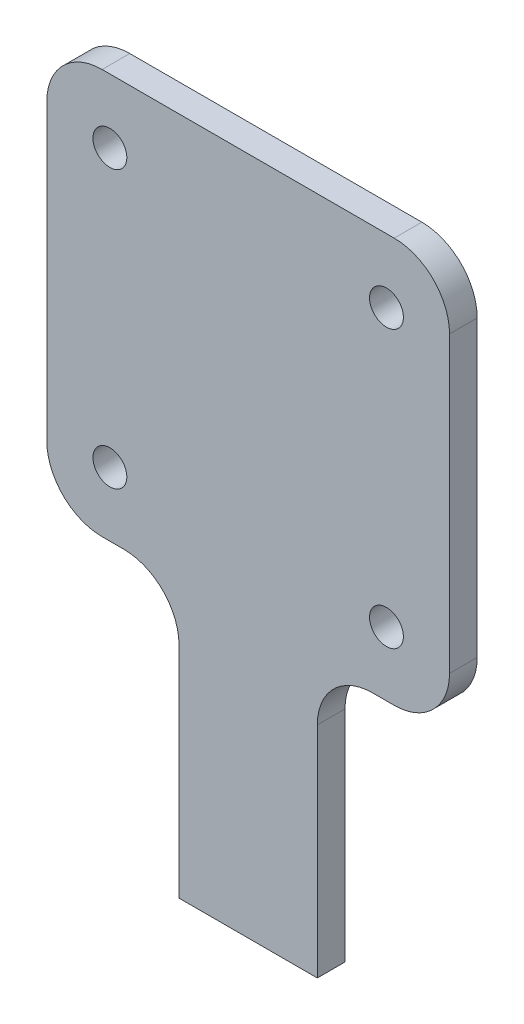
SolidWorks part; units mm, degrees
ref_plane "Front Plane" through (0, 0, 0) normal (0, 0, 1) x (1, 0, 0)
ref_plane "Top Plane" through (0, 0, 0) normal (0, 1, 0) x (1, 0, 0)
ref_plane "Right Plane" through (0, 0, 0) normal (1, 0, 0) x (0, 0, -1)
sketch "Sketch3" plane through (0, 0, 0) normal (0, 0, 1) x (1, 0, 0)
  line L0 (5, 19.8536) -> (14.56, 19.8536)
  line L2 (5, 19.8536) -> (5, 0)
  line L3 (5, 0) -> (-5, 0)
  line L4 (-5, 19.8536) -> (-5, 0)
  line L7 (-14.56, 49.1136) -> (14.56, 49.1136)
  line L8 (-14.56, 49.1136) -> (-14.56, 19.8536)
  line L9 (-14.56, 19.8536) -> (-5, 19.8536)
  line L10 (14.56, 49.1136) -> (14.56, 19.8536)
  line L13 (-14.56, 19.8536) -> (14.56, 19.8536) construction
  point P5 (0, 0)
  dimension "D1" = 10
extrude "Boss-Extrude1" add sketch "Sketch3" along normal mid plane 2
sketch "Sketch4" plane through (0, 0, -1) normal (0, 0, -1) x (-1, 0, 0)
  circle A0 centre (-10, 24.4836) radius 1.225 construction
  circle A1 centre (10, 24.4836) radius 1.225 construction
  circle A2 centre (10, 44.4836) radius 1.225 construction
  circle A3 centre (-10, 44.4836) radius 1.225 construction
  circle A4 centre (-10, 24.4836) radius 1.225
  circle A5 centre (10, 24.4836) radius 1.225
  circle A6 centre (10, 44.4836) radius 1.225
  circle A7 centre (-10, 44.4836) radius 1.225
  circle A8 centre (-10, 44.4836) radius 1.725
  circle A9 centre (10, 44.4836) radius 1.725
  circle A10 centre (-10, 24.4836) radius 1.725
  circle A11 centre (10, 24.4836) radius 1.725
  dimension "D1" = 0.5
extrude "Boss-Extrude2" add sketch "Sketch4" along normal blind 2
chamfer "Chamfer1" distance 2 angle 45 4 edges at (-11.725, 24.4836, -1) (8.275, 24.4836, -1) (-11.725, 44.4836, -1) (8.275, 44.4836, -1)
fillet "Fillet1" radius 4 6 edges at (-14.56, 19.8536, 0) (-14.56, 49.1136, 0) (14.56, 19.8536, 0) (14.56, 49.1136, 0) (-5, 19.8536, 0) (5, 19.8536, 0)
extrude "Cut-Extrude1" cut sketch "Sketch4<2>" against normal up to next contours A7 | A6 | A5 | A4 region at (10, 24.4836, -1) region at (-10, 24.4836, -1) region at (-10, 44.4836, -1) region at (10, 44.4836, -1)
sketch "Sketch4<2>" plane through (0, 0, -1) normal (0, 0, -1) x (-1, 0, 0) same geometry as "Sketch4"
